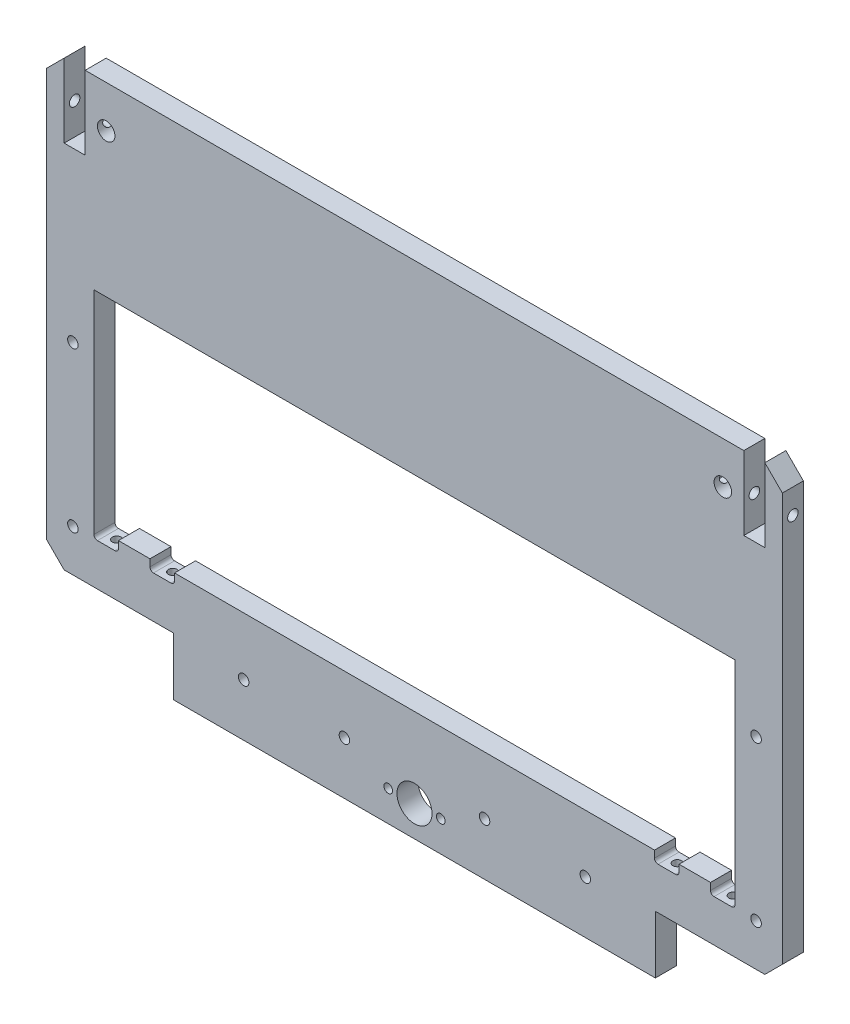
SolidWorks part; units mm, degrees
other "DetailItem1"
other "DetailItem2"
material "HDPE-green"
ref_plane "Front Plane" through (0, 0, 0) normal (0, 0, 1) x (1, 0, 0)
ref_plane "Top Plane" through (0, 0, 0) normal (0, 1, 0) x (1, 0, 0)
ref_plane "Right Plane" through (0, 0, 0) normal (1, 0, 0) x (0, 0, -1)
sketch "Sketch1" plane through (0, 0, 0) normal (0, 0, 1) x (1, 0, 0)
  line L1 (-137.5, -16.5) -> (137.5, -16.5)
  line L2 (-137.5, -16.5) -> (-137.5, 16.5)
  line L3 (-137.5, 16.5) -> (137.5, 16.5)
  line L4 (137.5, -16.5) -> (137.5, 16.5)
  line L5 (-137.5, -16.5) -> (137.5, 16.5) construction
  line L6 (-137.5, 16.5) -> (137.5, -16.5) construction
  point P0 (0, 0)
  dimension "D1" = 275
  dimension "D2" = 33
extrude "Boss-Extrude1" add sketch "Sketch1" along normal blind 12
sketch "Sketch2" plane through (0, 0, 12) normal (0, 0, 1) x (1, 0, 0)
  line L0 (137.5, 16.5) -> (-137.5, 16.5) construction
  line L1 (-15, 1) -> (21.5379, 1) construction
  circle A0 centre (0, 1) radius 10
  circle A1 centre (-15, 1) radius 2.5
  circle A2 centre (15, 1) radius 2.5
  point P2 (0, 16.5)
  dimension "D1" = 15.5
  dimension "D2" = 20
  dimension "D3" = 5
  dimension "D4" = 5
  dimension "D5" = 30
  dimension "D6" = 15
extrude "Cut-Extrude1" cut sketch "Sketch2" against normal up to next
sketch "Sketch3" plane through (0, 0, 12) normal (0, 0, 1) x (1, 0, 0)
  line L0 (-137.5, -16.5) -> (137.5, -16.5) construction
  line L1 (-210, 16.5) -> (210, 16.5)
  line L2 (-210, 16.5) -> (-210, 46.5)
  line L3 (-183, 46.5) -> (183, 46.5)
  line L4 (210, 16.5) -> (210, 46.5)
  line L5 (-183, 163.5) -> (183, 163.5)
  line L6 (-210, 46.5) -> (-210, 269.5)
  line L7 (-210, 269.5) -> (210, 269.5)
  line L8 (-183, 46.5) -> (-183, 163.5)
  line L11 (210, 46.5) -> (210, 269.5)
  line L13 (183, 46.5) -> (183, 163.5)
  circle A0 centre (0, 1) radius 10 construction
  dimension "D1" = 30
  dimension "D2" = 420
  dimension "D3" = 210
  dimension "D5" = 286
  dimension "D8" = 117
extrude "Boss-Extrude2" add sketch "Sketch3" against normal blind 12
sketch "Sketch4" plane through (0, 46.5, 0) normal (0, 1, 0) x (1, 0, 0)
  line L0 (-183, -6) -> (183, -6) construction
  line L1 (-183, 0) -> (-183, -12) construction
  line L2 (183, 0) -> (183, -12) construction
  line L4 (183, 0) -> (-183, 0) construction
  circle A0 centre (-144, -6) radius 2.5
  circle A1 centre (-176, -6) radius 2.5
  point P10 (0, 0)
  point P12 (0, 0)
  dimension "D1" = 5
  dimension "D2" = 5
  dimension "D3" = 144
  dimension "D4" = 176
extrude "Cut-Extrude2" cut sketch "Sketch4" against normal up to next
mirror "Mirror1" about plane through (0, 0, 0) normal (1, 0, 0) of "Cut-Extrude2"
sketch "Sketch5" plane through (0, 0, 12) normal (0, 0, 1) x (1, 0, 0)
  line L0 (-183, 46.5) -> (-183, 40.5)
  line L1 (-183, 40.5) -> (-169, 40.5)
  line L2 (-169, 40.5) -> (-169, 46.5)
  line L3 (183, 46.5) -> (-183, 46.5) construction
  line L4 (-169, 46.5) -> (-183, 46.5)
  line L5 (-151, 46.5) -> (-151, 40.5)
  line L6 (-151, 40.5) -> (-137, 40.5)
  line L7 (-137, 40.5) -> (-137, 46.5)
  line L8 (-151, 46.5) -> (-137, 46.5)
  circle A0 centre (0, 1) radius 10 construction
  dimension "D1" = 14
  dimension "D2" = 6
  dimension "D3" = 6
  dimension "D4" = 14
  dimension "D5" = 137
  dimension "D6" = 169
extrude "Cut-Extrude3" cut sketch "Sketch5" against normal up to next
fillet "Fillet1" radius 2 4 edges at (-137, 40.5, 6) (-151, 40.5, 6) (-169, 40.5, 6) (-183, 40.5, 6)
mirror "Mirror2" about plane through (0, 0, 0) normal (1, 0, 0) of "Fillet1", "Cut-Extrude3"
chamfer "Chamfer1" distance 10 angle 45 2 edges at (210, 16.5, 6) (-210, 16.5, 6)
sketch "Sketch8" plane through (0, 0, 12) normal (0, 0, 1) x (1, 0, 0)
  line L0 (0, 79.2288) -> (0, 236.3795) construction
  line L1 (210, 269.5) -> (-210, 269.5) construction
  line L2 (-188, 269.5) -> (-200, 269.5)
  line L3 (-188, 269.5) -> (-188, 227.5)
  line L4 (-188, 227.5) -> (-200, 227.5)
  line L5 (-200, 269.5) -> (-200, 227.5)
  line L7 (188, 269.5) -> (200, 269.5)
  line L8 (188, 269.5) -> (188, 227.5)
  line L9 (188, 227.5) -> (200, 227.5)
  line L10 (200, 269.5) -> (200, 227.5)
  dimension "D1" = 376
  dimension "D2" = 188
  dimension "D3" = 12
  dimension "D4" = 12
  dimension "D5" = 42
  dimension "D6" = 42
extrude "Cut-Extrude6" cut sketch "Sketch8" against normal up to next
chamfer "Chamfer2" distance 10 angle 45 2 edges at (210, 269.5, 6) (-210, 269.5, 6)
hole_wizard "Ø6.0 (6) Diameter Hole1" positions "Sketch10" profile "Sketch9" hole size "Ø6.0" standard "ISO" end condition up to next
sketch "Sketch10" plane through (0, 0, 0) normal (0, 0, -1) x (-1, 0, 0)
  line L0 (183, 163.5) -> (183, 42.5) construction
  line L1 (200, 16.5) -> (137.5, 16.5) construction
  point P0 (195, 131.5)
  point P1 (195, 40.5)
  dimension "D1" = 12
  dimension "D2" = 12
  dimension "D3" = 115
  dimension "D4" = 24
sketch "Sketch9" plane through (-195, 131.5, 0) normal (1, 0, 0) x (0, 1, 0)
  line L0 (0, 0) -> (0, 12.001)
  line L1 (0, 12.001) -> (3, 12.001)
  line L2 (3, 12.001) -> (3, 0)
  line L5 (3, 0) -> (0, 0)
  line L11 (0, -6.35) -> (0, 107.95) construction
  dimension "Thru Hole Dia." = 6
  dimension "Thru Hole Depth" = 12.001
hole_wizard "Ø10.0 (10) Diameter Hole1" positions "Sketch12" profile "Sketch11" hole size "Ø10.0" standard "ISO" end condition up to next
sketch "Sketch12" plane through (0, 0, 0) normal (0, 0, -1) x (-1, 0, 0)
  line L0 (188, 227.5) -> (188, 269.5) construction
  line L1 (-188, 269.5) -> (188, 269.5) construction
  point P0 (176, 245.5)
  dimension "D1" = 12
  dimension "D2" = 24
sketch "Sketch11" plane through (-176, 245.5, 0) normal (1, 0, 0) x (0, 1, 0)
  line L0 (0, 0) -> (0, 12.001)
  line L1 (0, 12.001) -> (5, 12.001)
  line L2 (5, 12.001) -> (5, 0)
  line L5 (5, 0) -> (0, 0)
  line L11 (0, -6.35) -> (0, 107.95) construction
  dimension "Thru Hole Dia." = 10
  dimension "Thru Hole Depth" = 12.001
hole_wizard "Ø6.0 (6) Diameter Hole2" positions "Sketch14" profile "Sketch13" hole size "Ø6.0" standard "ISO"
sketch "Sketch14" plane through (-188, 0, 0) normal (-1, 0, 0) x (0, 0, 1)
  line L0 (0, 227.5) -> (0, 269.5) construction
  line L1 (0, 269.5) -> (12, 269.5) construction
  point P0 (6, 245.5)
  dimension "D1" = 6
  dimension "D2" = 24
sketch "Sketch13" plane through (-188, 245.5, 6) normal (0, 1, 0) x (0, 0, 1)
  line L0 (0, 0) -> (0, 21.8026)
  line L1 (0, 21.8026) -> (3, 20)
  line L2 (3, 20) -> (3, 0)
  line L5 (3, 0) -> (0, 0)
  line L10 (0, 21.8026) -> (-3, 20) construction
  line L11 (0, -6.35) -> (0, 107.95) construction
  dimension "Hole Dia." = 6
  dimension "Hole Depth" = 20
  dimension "Drill Angle" = 118
hole_wizard "Ø6.0 (6) Diameter Hole3" positions "Sketch16" profile "Sketch15" hole size "Ø6.0" standard "ISO"
sketch "Sketch16" plane through (-210, 0, 0) normal (-1, 0, 0) x (0, 0, 1)
  line L0 (0, 259.5) -> (0, 26.5) construction
  line L1 (0, 269.5) -> (12, 269.5) construction
  point P0 (6, 245.5)
  dimension "D1" = 6
  dimension "D2" = 24
sketch "Sketch15" plane through (-210, 245.5, 6) normal (0, 1, 0) x (0, 0, 1)
  line L0 (0, 0) -> (0, 21.8026)
  line L1 (0, 21.8026) -> (3, 20)
  line L2 (3, 20) -> (3, 0)
  line L5 (3, 0) -> (0, 0)
  line L10 (0, 21.8026) -> (-3, 20) construction
  line L11 (0, -6.35) -> (0, 107.95) construction
  dimension "Hole Dia." = 6
  dimension "Hole Depth" = 20
  dimension "Drill Angle" = 118
mirror "Mirror3" about plane through (0, 0, 0) normal (1, 0, 0) of "Ø6.0 (6) Diameter Hole3", "Ø10.0 (10) Diameter Hole1", "Ø6.0 (6) Diameter Hole2", "Ø6.0 (6) Diameter Hole1"
hole_wizard "Ø6.0 (6) Diameter Hole4" positions "Sketch18" profile "Sketch17" hole size "Ø6.0" standard "ISO" end condition up to next
sketch "Sketch18" plane through (0, 0, 0) normal (0, 0, -1) x (-1, 0, 0)
  line L0 (137.5, -16.5) -> (-137.5, -16.5) construction
  line L1 (137.5, 16.5) -> (137.5, -16.5) construction
  line L2 (-137.5, -16.5) -> (-137.5, 16.5) construction
  circle A0 centre (0, 1) radius 10 construction
  point P0 (-97.5, 13.5)
  point P1 (-40, 13.5)
  point P3 (40, 13.5)
  point P5 (97.5, 13.5)
  dimension "D1" = 30
  dimension "D2" = 30
  dimension "D3" = 30
  dimension "D4" = 30
  dimension "D5" = 40
  dimension "D6" = 40
  dimension "D7" = 40
  dimension "D8" = 40
sketch "Sketch17" plane through (97.5, 13.5, 0) normal (1, 0, 0) x (0, 1, 0)
  line L0 (0, 0) -> (0, 12)
  line L1 (0, 12) -> (3, 12)
  line L2 (3, 12) -> (3, 0)
  line L5 (3, 0) -> (0, 0)
  line L11 (0, -6.35) -> (0, 107.95) construction
  dimension "Thru Hole Dia." = 6
  dimension "Thru Hole Depth" = 12
